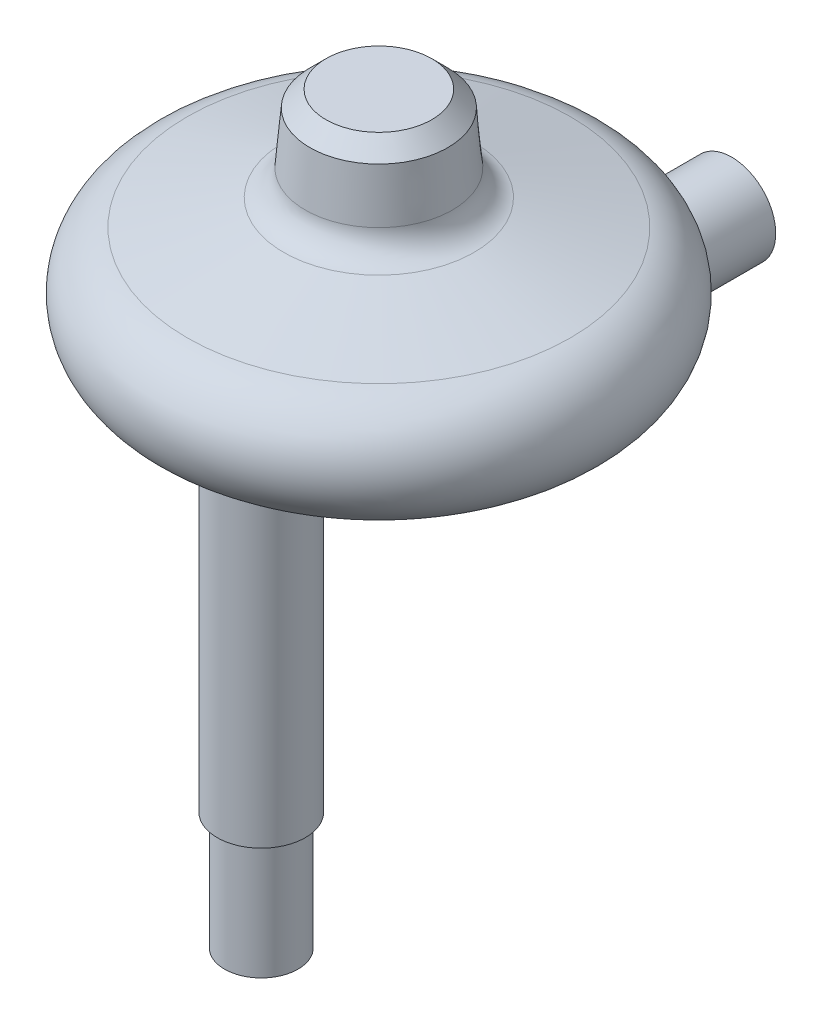
SolidWorks part; units mm, degrees
material "3003 Alloy"
ref_plane "Front" through (0, 0, 0) normal (0, 0, 1) x (1, 0, 0)
ref_plane "Top" through (0, 0, 0) normal (0, 1, 0) x (1, 0, 0)
ref_plane "Right" through (0, 0, 0) normal (1, 0, 0) x (0, 0, -1)
sketch "Sketch1" plane through (0, 0, 0) normal (0, 0, 1) x (1, 0, 0)
  line L0 (0, 0) -> (0, 69.3536) construction
  line L1 (0, 0) -> (19.05, 0)
  line L2 (20.6935, 12.4836) -> (0, 18.0284)
  line L4 (0, 18.0284) -> (0, 0)
  arc A0 (19.05, 0) -> (20.6935, 12.4836) centre (19.05, 6.35) ccw
  dimension "D2" = 6.35
  dimension "D1" = 50.8
  dimension "D3" = 15
revolve "Base-Revolve" add sketch "Sketch1" angle 360 about L0
sketch "Sketch2" plane through (0, 0, 0) normal (0, -1, 0) x (1, 0, 0)
  circle A0 centre (0, 0) radius 9.525
  dimension "D1" = 19.05
extrude "Boss-Extrude1" add sketch "Sketch2" against normal blind 25.4 draft 5
fillet "Fillet1" radius 3.175 1 edges at (0, 15.8477, 8.1385)
sketch "Sketch3" plane through (0, 0, 0) normal (0, -1, 0) x (1, 0, 0)
  circle A0 centre (0, 12.7) radius 4.7625
  dimension "D1" = 9.525
  dimension "D2" = 12.7
extrude "Boss-Extrude2" add sketch "Sketch3" along normal blind 35.875
fillet "Fillet2" radius 3.175 1 edges at (0, 0, 7.9375)
ref_plane "Plane4" through (0, 0, -6.35) normal (0, 0, 1) x (1, 0, 0)
sketch "Sketch4" plane through (0, 0, -6.35) normal (0, 0, 1) x (1, 0, 0)
  line L1 (-4.7625, 1.5875) -> (4.7625, 1.5875)
  line L2 (-4.7625, 1.5875) -> (-4.7625, -4.7625)
  line L3 (4.7625, -4.7625) -> (4.7625, 1.5875)
  line L4 (-19.05, 0) -> (19.05, 0) construction
  arc A0 (-4.7625, -4.7625) -> (4.7625, -4.7625) centre (0, -4.7625) ccw
  dimension "D1" = 4.7625
  dimension "D2" = 6.35
  dimension "D3" = 1.5875
extrude "Boss-Extrude3" add sketch "Sketch4" against normal blind 19.05
fillet "Fillet4" radius 1.5875 3 edges at (4.7625, -2.3812, -6.35) (0, -9.525, -6.35) (-4.7625, -2.3812, -6.35)
fillet "Fillet8" radius 1.5875 7 edges at (4.7625, 12.0396, -15.5158) (4.7625, 0, -13.1913) (4.2975, 0, -6.815) (0, 0, -6.35) (-4.2975, 0, -6.815) (-4.7625, 12.5632, -17.0875) (-4.7625, 0, -13.1913)
chamfer "Chamfer1" distance 1.5875 angle 45 1 edges at (0, 25.4, -7.3028) first distance on face at (0, 25.4, -7.3028)
sketch "Sketch5" plane through (0, 0, -25.4) normal (0, 0, -1) x (-1, 0, 0)
  circle A0 centre (0, -4.7625) radius 4.7625
  arc A1 (-4.7625, -4.7625) -> (4.7625, -4.7625) centre (0, -4.7625) ccw construction
extrude "Boss-Extrude4" add sketch "Sketch5" along normal blind 12.7
sketch "Sketch6" plane through (0, -35.875, 0) normal (0, -1, 0) x (1, 0, 0)
  circle A1 centre (0, 12.7) radius 3.9687
  circle A2 centre (0, 12.7) radius 3.9687
  dimension "D1" = 0.7937
extrude "Boss-Extrude5" add sketch "Sketch6" along normal blind 12.7
